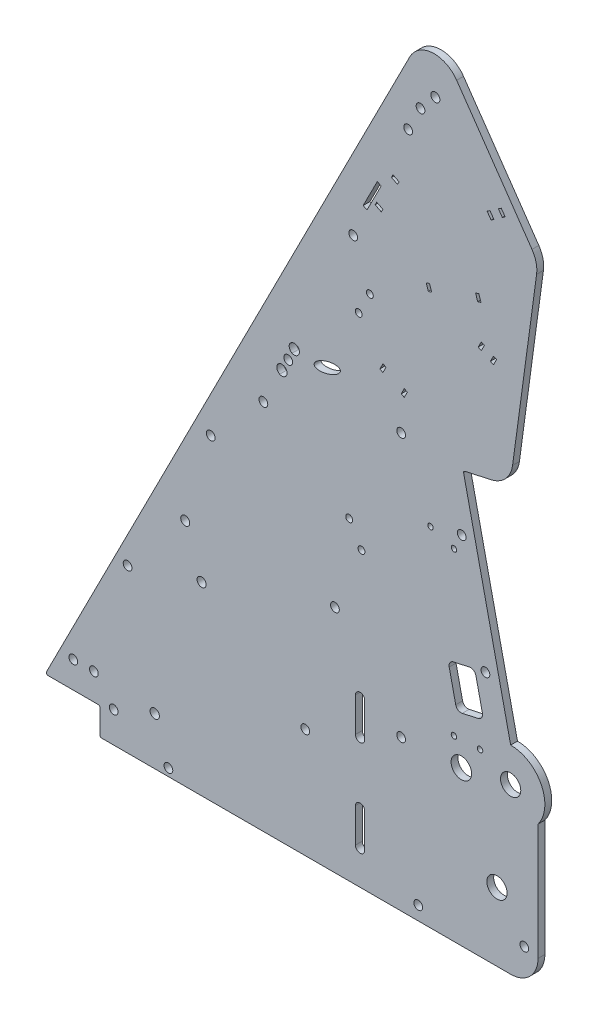
SolidWorks part; units mm, degrees
other "Markup1"
sketch "Sketch5"
ref_plane "Front Plane" through (0, 0, 0) normal (0, 0, 1) x (1, 0, 0)
ref_plane "Top Plane" through (0, 0, 0) normal (0, 1, 0) x (1, 0, 0)
ref_plane "Right Plane" through (0, 0, 0) normal (1, 0, 0) x (0, 0, -1)
sketch "Sketch1" plane through (0, 0, 0) normal (0, 0, 1) x (1, 0, 0)
  line L1 (228.6, -12.7) -> (228.6, 53.975)
  line L2 (178.7547, 351.4131) -> (0, 0)
  line L3 (228.6, 279.4) -> (178.7547, 351.4131)
  line L5 (0, 0) -> (25.4, 0)
  line L6 (25.4, 0) -> (25.4, -12.7)
  line L7 (25.4, -12.7) -> (228.6, -12.7)
  line L9 (215.9, 79.375) -> (193.9097, 178.5667)
  line L10 (193.9097, 178.5667) -> (215.6079, 183.377)
  line L11 (215.6079, 183.377) -> (228.6, 279.4)
  arc A0 (228.6, 53.975) -> (215.9, 79.375) centre (215.9, 63.5) ccw
  dimension "D7" = 12.7
  dimension "D8" = 76.2
  dimension "D10" = 31.75
  dimension "D2" = 292.1
  dimension "D3" = 25.4
  dimension "D4" = 215.9
  dimension "D5" = 394.2644
  dimension "D6" = 203.2
  dimension "D9" = 63.039
  dimension "D11" = 101.6
  dimension "D12" = 12.5
  dimension "D13" = 22.225
extrude "Boss-Extrude1" add sketch "Sketch1" along normal blind 3.175
sketch "Sketch2" plane through (0, 0, 3.175) normal (0, 0, 1) x (1, 0, 0)
  line L0 (178.7547, 351.4131) -> (0, 0) construction
  line L1 (25.4, -12.7) -> (228.6, -12.7) construction
  line L2 (215.9, 79.375) -> (193.9097, 178.5667) construction
  line L3 (193.9097, 178.5667) -> (215.6079, 183.377) construction
  line L4 (215.9, 79.375) -> (193.9097, 178.5667) construction
  line L5 (64.9432, 94.0578) -> (72.5445, 73.1732) construction
  line L6 (64.9432, 94.0578) -> (89.8317, 94.0578) construction
  line L10 (228.6, -12.7) -> (228.6, 53.975) construction
  circle A0 centre (64.9432, 94.0578) radius 2.0955
  circle A1 centre (180.975, 322.1643) radius 2.0955
  circle A2 centre (72.5445, 73.1732) radius 2.0955
  circle A3 centre (193.2078, 152.3944) radius 2.032
  circle A4 centre (215.9, 63.5) radius 4.699
  circle A7 centre (173.0375, -6.35) radius 2.032
  circle A8 centre (204.203, 102.7985) radius 2.032
  circle A26 centre (209.55, 19.05) radius 4.699
  arc A30 (228.6, 53.975) -> (215.9, 79.375) centre (215.9, 63.5) ccw construction
  circle A31 centre (165.1, 179.3875) radius 2.032
  dimension "D3" = 4.191
  dimension "D5" = 4.191
  dimension "D9" = 4.191
  dimension "D20" = 9.398
  dimension "D23" = 9.398
  dimension "D18" = 4.064
  dimension "D26" = 4.064
  dimension "D14" = 4.064
  dimension "D2" = 15.24
  dimension "D6" = 15.24
  dimension "D7" = 22.225
  dimension "D21" = 44.45
  dimension "D22" = 6.35
  dimension "D19" = 160.3375
  dimension "D24" = 44.45
  dimension "D25" = 6.35
  dimension "D27" = 25.4
  dimension "D28" = 50.8
  dimension "D29" = 6.35
  dimension "D17" = 6.35
  dimension "D33" = 55.5625
  dimension "D15" = 114.3
  dimension "D4" = 180.975
  dimension "D8" = 70
extrude "Cut-Extrude1" cut sketch "Sketch2" against normal through all
sketch "Sketch7" plane through (0, 0, 3.175) normal (0, 0, 1) x (1, 0, 0)
  line L0 (146.05, 3.175) -> (146.05, 19.05) construction
  line L1 (143.891, 3.175) -> (143.891, 19.05)
  line L2 (148.209, 3.175) -> (148.209, 19.05)
  line L3 (146.05, 47.625) -> (146.05, 63.5) construction
  line L4 (143.891, 47.625) -> (143.891, 63.5)
  line L5 (148.209, 47.625) -> (148.209, 63.5)
  line L6 (25.4, -12.7) -> (228.6, -12.7) construction
  line L12 (228.6, -12.7) -> (228.6, 53.975) construction
  line L13 (25.4, -12.7) -> (228.6, -12.7) construction
  arc A0 (143.891, 3.175) -> (148.209, 3.175) centre (146.05, 3.175) ccw
  arc A1 (148.209, 19.05) -> (143.891, 19.05) centre (146.05, 19.05) ccw
  arc A2 (143.891, 47.625) -> (148.209, 47.625) centre (146.05, 47.625) ccw
  arc A3 (148.209, 63.5) -> (143.891, 63.5) centre (146.05, 63.5) ccw
  circle A8 centre (50.8, 9.525) radius 2.159
  circle A10 centre (134.3935, 93.98) radius 2.032 construction
  circle A11 centre (134.3935, 93.98) radius 2.032
  point P2 (146.05, 11.1125)
  point P9 (146.05, 55.5625)
  dimension "D1" = 4.318
  dimension "D5" = 4.318
  dimension "D2" = 15.875
  dimension "D3" = 15.875
  dimension "D4" = 44.45
  dimension "D6" = 95.25
  dimension "D7" = 82.55
  dimension "D8" = 15.875
  dimension "D9" = 22.225
extrude "Cut-Extrude2" cut sketch "Sketch7" against normal through all
sketch "Sketch10" plane through (0, 0, 3.175) normal (0, 0, 1) x (1, 0, 0)
  circle A1 centre (165.1, 57.15) radius 2.032
  circle A2 centre (120.65, 38.1) radius 2.032
  circle A3 centre (13.0465, 12.3347) radius 2.032
  circle A4 centre (22.5715, 12.3347) radius 2.032
  circle A5 centre (38.2114, 62.6398) radius 2.032
  dimension "D1" = 4.064
  dimension "D2" = 4.064
  dimension "D4" = 63.5
  dimension "D5" = 69.85
extrude "Cut-Extrude3" cut sketch "Sketch10" against normal up to next
fillet "Fillet1" radius 12.7 4 edges at (228.6, -12.7, 1.5875) (178.7547, 351.4131, 1.5875) (215.6079, 183.377, 1.5875) (228.6, 279.4, 1.5875)
fillet "Fillet2" radius 0.7937 4 edges at (25.4, -12.7, 1.5875) (25.4, 0, 1.5875) (193.9097, 178.5667, 1.5875) (0, 0, 1.5875)
sketch "Sketch12" plane through (0, 0, 3.175) normal (0, 0, 1) x (1, 0, 0)
  circle A0 centre (31.75, 1.5875) radius 2.032
  circle A1 centre (222.25, 1.5875) radius 2.032
  circle A2 centre (57.15, -9.2075) radius 2.032
  circle A3 centre (57.15, -9.2075) radius 2.286 construction
  dimension "D1" = 4.064
  dimension "D2" = 4.064
extrude "Cut-Extrude5" cut sketch "Sketch12" against normal through all
sketch "Sketch13" plane through (0, 0, 3.175) normal (0, 0, 1) x (1, 0, 0)
  line L2 (194.6847, 178.7385) -> (206.9592, 181.4597) construction
  line L5 (199.2434, 101.699) -> (189.6226, 145.0954) construction
  line L6 (189.6022, 69.9806) -> (201.7089, 70.5092) construction
  line L7 (186.8444, 98.9502) -> (199.2434, 101.699)
  line L8 (186.8444, 98.9502) -> (190.9676, 80.3518)
  line L9 (190.9676, 80.3518) -> (203.3665, 83.1006)
  line L10 (199.2434, 101.699) -> (203.3665, 83.1006)
  line L11 (189.6022, 69.9806) -> (190.9676, 80.3518) construction
  line L12 (201.7089, 70.5092) -> (203.3665, 83.1006) construction
  line L13 (215.9, 79.375) -> (194.0815, 177.7917) construction
  line L14 (178.7216, 148.5324) -> (189.6226, 145.0954) construction
  circle A0 centre (189.6022, 69.9806) radius 1.27
  circle A1 centre (201.7089, 70.5092) radius 1.27
  circle A2 centre (178.7216, 148.5324) radius 1.27
  circle A3 centre (189.6226, 145.0954) radius 1.27
  dimension "D7" = 2.54
  dimension "D2" = 11.43
  dimension "D3" = 76.2
  dimension "D4" = 12.7
  dimension "D5" = 19.05
  dimension "D6" = 120
  dimension "D8" = 110
  dimension "D9" = 80
  dimension "D10" = 12.7
  dimension "D11" = 44.45
  dimension "D12" = 11.43
extrude "Cut-Extrude6" cut sketch "Sketch13" against normal through all both and the other way through all
sketch "Sketch14" plane through (0, 0, 3.175) normal (0, 0, 1) x (1, 0, 0)
  line L0 (26.1937, -12.7) -> (215.9, -12.7) construction
  line L1 (228.6, 0) -> (228.6, 53.975) construction
  line L2 (112.7125, 182.5625) -> (101.1964, 159.9231) construction
  line L3 (169.1053, 332.4434) -> (0.5868, 1.1536) construction
  line L4 (112.7125, 182.5625) -> (136.864, 190.4279) construction
  line L5 (147.4827, 261.9243) -> (154.0469, 274.8287)
  line L6 (147.4827, 261.9243) -> (149.2654, 261.0175)
  line L7 (154.0469, 274.8287) -> (155.8295, 273.922)
  line L8 (149.2654, 261.0175) -> (155.8295, 273.922)
  line L9 (169.1053, 332.4434) -> (0.5868, 1.1536) construction
  line L10 (160.5905, 279.7801) -> (161.3102, 281.1951)
  line L11 (160.5905, 279.7801) -> (163.4204, 278.3406)
  line L12 (161.3102, 281.1951) -> (164.1402, 279.7556)
  line L13 (163.4204, 278.3406) -> (164.1402, 279.7556)
  line L14 (153.7897, 266.4104) -> (156.6196, 264.9709)
  line L15 (153.7897, 266.4104) -> (153.0699, 264.9954)
  line L16 (156.6196, 264.9709) -> (155.8998, 263.5559)
  line L17 (153.0699, 264.9954) -> (155.8998, 263.5559)
  line L18 (162.6248, 261.9162) -> (152.3747, 267.1302) construction
  line L19 (178.2697, 245.9923) -> (179.2404, 242.9693)
  line L20 (178.2697, 245.9923) -> (176.7582, 245.5069)
  line L21 (179.2404, 242.9693) -> (177.7289, 242.4839)
  line L22 (176.7582, 245.5069) -> (177.7289, 242.4839)
  line L23 (178.1316, 240.7894) -> (185.2951, 254.8722) construction
  line L24 (200.6096, 249.8308) -> (199.639, 252.8538)
  line L25 (200.6096, 249.8308) -> (202.1211, 250.3161)
  line L26 (199.639, 252.8538) -> (201.1505, 253.3391)
  line L27 (202.1211, 250.3161) -> (201.1505, 253.3391)
  line L28 (198.6169, 250.8445) -> (203.0585, 248.5852) construction
  line L29 (199.3876, 252.3597) -> (200.1584, 253.8749) construction
  line L30 (180.2625, 244.9786) -> (175.0037, 247.6536) construction
  line L31 (169.4256, 275.2859) -> (159.1755, 280.4999) construction
  line L32 (149.4273, 265.7471) -> (149.0052, 264.9173) construction
  line L33 (150.7878, 264.0106) -> (151.2099, 264.8403) construction
  line L62 (156.643, 199.3999) -> (158.0826, 202.2298)
  line L63 (156.643, 199.3999) -> (155.2281, 200.1197)
  line L64 (158.0826, 202.2298) -> (156.6676, 202.9496)
  line L65 (155.2281, 200.1197) -> (156.6676, 202.9496)
  line L66 (165.1328, 195.0814) -> (166.5723, 197.9113)
  line L67 (165.1328, 195.0814) -> (166.5478, 194.3617)
  line L68 (166.5723, 197.9113) -> (167.9873, 197.1916)
  line L69 (166.5478, 194.3617) -> (167.9873, 197.1916)
  line L79 (202.2945, 234.5568) -> (200.855, 231.7269)
  line L80 (202.2945, 234.5568) -> (203.7094, 233.8371)
  line L81 (200.855, 231.7269) -> (202.2699, 231.0072)
  line L82 (203.7094, 233.8371) -> (202.2699, 231.0072)
  line L83 (206.5148, 228.8479) -> (207.9543, 231.6778)
  line L84 (206.5148, 228.8479) -> (207.9298, 228.1282)
  line L85 (207.9543, 231.6778) -> (209.3693, 230.9581)
  line L86 (207.9298, 228.1282) -> (209.3693, 230.9581)
  line L87 (195.7191, 232.1346) -> (203.6489, 247.7238) construction
  line L88 (205.014, 288.3715) -> (206.821, 285.7609)
  line L89 (205.014, 288.3715) -> (206.3193, 289.275)
  line L90 (206.821, 285.7609) -> (208.1263, 286.6644)
  line L91 (206.3193, 289.275) -> (208.1263, 286.6644)
  line L92 (210.2352, 291.9855) -> (212.0422, 289.3749)
  line L93 (210.2352, 291.9855) -> (211.5405, 292.889)
  line L94 (212.0422, 289.3749) -> (213.3475, 290.2784)
  line L95 (211.5405, 292.889) -> (213.3475, 290.2784)
  line L96 (225.7968, 283.4499) -> (190.8675, 333.9133) construction
  circle A0 centre (142.875, 247.65) radius 2.032
  circle A1 centre (112.7125, 182.5625) radius 2.032
  circle A2 centre (101.1964, 159.9231) radius 2.032
  circle A3 centre (150.594, 227.8985) radius 1.6 construction
  circle A4 centre (145.4254, 217.7376) radius 1.6 construction
  circle A5 centre (141.0058, 132.9805) radius 1.6 construction
  circle A6 centre (146.7058, 123.1079) radius 1.6 construction
  circle A7 centre (150.594, 227.8985) radius 1.6
  circle A8 centre (145.4254, 217.7376) radius 1.6
  circle A9 centre (141.0058, 132.9805) radius 1.6
  circle A10 centre (146.7058, 123.1079) radius 1.6
  ellipse E0 centre (109.8335, 176.9027) end of major axis (108.7539, 174.7802) minor radius 2.32 (108.7539, 174.7802) -> (110.9131, 179.0251) ccw construction
  ellipse E1 centre (109.8335, 176.9027) end of major axis (108.7539, 174.7802) minor radius 2.32 (108.7539, 174.7802) -> (110.9131, 179.0251) ccw
  ellipse E2 centre (130.8261, 188.4615) end of major axis (124.7883, 186.4952) minor radius 2.3812
  ellipse E3 centre (115.5915, 188.2223) end of major axis (114.5119, 186.0999) minor radius 2.32 (114.5119, 186.0999) -> (116.6711, 190.3448) ccw construction
  ellipse E4 centre (115.5915, 188.2223) end of major axis (114.5119, 186.0999) minor radius 2.32 (114.5119, 186.0999) -> (116.6711, 190.3448) ccw
  spline S0 degree 3 poles (603.8918, 1049.0657) (-166.9189, -675.3083) (147.8077, 168.3802) (110.3225, 179.2425) (110.1654, 179.2721) (109.6955, 179.3152) (109.3734, 179.2831) (108.9218, 179.1456) (108.7737, 179.0841) (108.4954, 178.9343) (108.365, 178.8464) (108.1219, 178.6442) (108.0097, 178.5297) (107.8134, 178.2839) (107.7278, 178.1512) (107.5834, 177.8672) (107.527, 177.7202) (107.4441, 177.4168) (107.4178, 177.2585) (107.3978, 176.9432) (107.4036, 176.7863) (107.4465, 176.4736) (107.4841, 176.3175) (107.5874, 176.0205) (107.6532, 175.8777) (107.8133, 175.6037) (107.9066, 175.4748) (114.8282, 167.6036) (173.9427, 200.577) (-567.4982, 911.3293) knots -15.287416 -15.287416 -15.287416 -15.287416 0.0625 0.0625 0.125 0.125 0.25 0.25 0.3125 0.3125 0.375 0.375 0.4375 0.4375 0.5 0.5 0.5625 0.5625 0.625 0.625 0.6875 0.6875 0.75 0.75 0.8125 0.8125 0.875 0.875 4.983329 4.983329 4.983329 4.983329 only from (110.9131, 179.0251) to (108.7539, 174.7802) construction
  spline S1 degree 3 poles (110.9131, 179.0251) (110.7727, 179.0965) (110.6265, 179.1544) (110.3225, 179.2425) (110.1654, 179.2721) (109.6955, 179.3152) (109.3734, 179.2831) (108.9218, 179.1456) (108.7737, 179.0841) (108.4954, 178.9343) (108.365, 178.8464) (108.1219, 178.6442) (108.0097, 178.5297) (107.8134, 178.2839) (107.7278, 178.1512) (107.5834, 177.8672) (107.527, 177.7202) (107.4441, 177.4168) (107.4178, 177.2585) (107.3978, 176.9432) (107.4036, 176.7863) (107.4465, 176.4736) (107.4841, 176.3175) (107.5874, 176.0205) (107.6532, 175.8777) (107.8133, 175.6037) (107.9066, 175.4748) (108.2178, 175.121) (108.4736, 174.9228) (108.7539, 174.7802) knots 0 0 0 0 0.0625 0.0625 0.125 0.125 0.25 0.25 0.3125 0.3125 0.375 0.375 0.4375 0.4375 0.5 0.5 0.5625 0.5625 0.625 0.625 0.6875 0.6875 0.75 0.75 0.8125 0.8125 0.875 0.875 1 1 1 1
  spline S2 degree 3 poles (-635.3332, 847.705) (160.0375, 206.8561) (120.8424, 181.1302) (113.9875, 186.4501) (113.8729, 186.5577) (113.5583, 186.9155) (113.3974, 187.1901) (113.2413, 187.6401) (113.2046, 187.793) (113.1618, 188.1044) (113.1558, 188.2648) (113.176, 188.5797) (113.2018, 188.7347) (113.2848, 189.0394) (113.3426, 189.1891) (113.5563, 189.6095) (113.7586, 189.8627) (114.1212, 190.1647) (114.2542, 190.2544) (114.5324, 190.4041) (114.6775, 190.4645) (114.9798, 190.5567) (115.1369, 190.5882) (115.4499, 190.6199) (115.6074, 190.6207) (115.9244, 190.5918) (116.0795, 190.5623) (125.0451, 187.9725) (125.4505, 134.6135) (-868.6048, 361.2821) knots -3.325634 -3.325634 -3.325634 -3.325634 0.0625 0.0625 0.125 0.125 0.25 0.25 0.3125 0.3125 0.375 0.375 0.4375 0.4375 0.5 0.5 0.625 0.625 0.6875 0.6875 0.75 0.75 0.8125 0.8125 0.875 0.875 0.9375 0.9375 4.586013 4.586013 4.586013 4.586013 only from (114.5119, 186.0999) to (116.6711, 190.3448) construction
  spline S3 degree 3 poles (114.5119, 186.0999) (114.3711, 186.1715) (114.2359, 186.2574) (113.9875, 186.4501) (113.8729, 186.5577) (113.5583, 186.9155) (113.3974, 187.1901) (113.2413, 187.6401) (113.2046, 187.793) (113.1618, 188.1044) (113.1558, 188.2648) (113.176, 188.5797) (113.2018, 188.7347) (113.2848, 189.0394) (113.3426, 189.1891) (113.5563, 189.6095) (113.7586, 189.8627) (114.1212, 190.1647) (114.2542, 190.2544) (114.5324, 190.4041) (114.6775, 190.4645) (114.9798, 190.5567) (115.1369, 190.5882) (115.4499, 190.6199) (115.6074, 190.6207) (115.9244, 190.5918) (116.0795, 190.5623) (116.3815, 190.4751) (116.53, 190.4166) (116.6711, 190.3448) knots 0 0 0 0 0.0625 0.0625 0.125 0.125 0.25 0.25 0.3125 0.3125 0.375 0.375 0.4375 0.4375 0.5 0.5 0.625 0.625 0.6875 0.6875 0.75 0.75 0.8125 0.8125 0.875 0.875 0.9375 0.9375 1 1 1 1
  point P89 (0, 0)
  dimension "D1" = 4.064
  dimension "D15" = 3.175
  dimension "D2" = 195.2625
  dimension "D3" = 115.8875
  dimension "D4" = 85.725
  dimension "D5" = 260.35
  dimension "D6" = 25.4
  dimension "D7" = 4.7625
  dimension "D8" = 12.7
  dimension "D9" = 19.05
  dimension "D10" = 45
  dimension "D11" = 6.858
  dimension "D12" = 7.62
  dimension "D13" = 3.175
  dimension "D14" = 1.5875
  dimension "D16" = 1.5875
  dimension "D17" = 1.5875
  dimension "D18" = 9.525
  dimension "D19" = 47.625
  dimension "D20" = 38.1
  dimension "D27" = 4.7625
  dimension "D28" = 1.5875
  dimension "D29" = 3.175
  dimension "D30" = 4.7625
  dimension "D31" = 9.525
  dimension "D32" = 4.7625
  dimension "D33" = 1.5875
  dimension "D34" = 3.175
  dimension "D35" = 6.35
  dimension "D36" = 12.7
extrude "Cut-Extrude7" cut sketch "Sketch14" against normal up to next
sketch "Sketch15" plane through (0, 0, 3.175) normal (0, 0, 1) x (1, 0, 0)
  line L0 (169.1053, 332.4434) -> (0.5868, 1.1536) construction
  circle A0 centre (76.7868, 134.1481) radius 2.032
  circle A1 centre (174.0994, 314.25) radius 2.032
  circle A2 centre (168.3414, 302.9303) radius 2.032
  circle A3 centre (174.0994, 314.25) radius 1.905 construction
  circle A4 centre (168.3414, 302.9303) radius 1.905 construction
  dimension "D1" = 4.064
  dimension "D4" = 4.064
  dimension "D2" = 7.62
  dimension "D3" = 76.2
extrude "Cut-Extrude8" cut sketch "Sketch15" against normal through all
fillet "Fillet3" radius 2.54 4 edges at (199.2434, 101.699, 1.5875) (186.8444, 98.9502, 1.5875) (190.9676, 80.3518, 1.5875) (203.3665, 83.1006, 1.5875)
sketch "Sketch16" plane through (0, 0, 3.175) normal (0, 0, 1) x (1, 0, 0)
  line L0 (228.6, 0) -> (228.6, 53.975) construction
  line L1 (26.1937, -12.7) -> (215.9, -12.7) construction
  circle A0 centre (193.04, 58.801) radius 4.7625
  dimension "D1" = 9.525
  dimension "D2" = 35.56
  dimension "D3" = 71.501
extrude "Cut-Extrude9" cut sketch "Sketch16" against normal through all
equation "\"D6@Sketch2\"=\"D2@Sketch2\""
